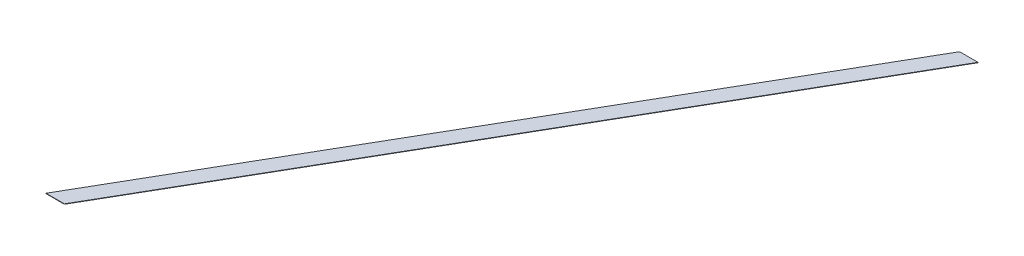
SolidWorks part; units mm, degrees
ref_plane "Front Plane" through (0, 0, 0) normal (0, 0, 1) x (1, 0, 0)
ref_plane "Top Plane" through (0, 0, 0) normal (0, 1, 0) x (1, 0, 0)
ref_plane "Right Plane" through (0, 0, 0) normal (1, 0, 0) x (0, 0, -1)
sketch "Sketch1" plane through (0, 0, 0) normal (0, 1, 0) x (1, 0, 0)
  line L0 (0, 0) -> (0, 101.6615)
  line L1 (0, 101.6615) -> (1523.0785, 2741.8387)
  line L2 (1523.0785, 2741.8387) -> (1581.7255, 2741.8387)
  line L3 (1581.7255, 2741.8387) -> (0, 0)
  line L4 (456.7373, 893.3918) -> (515.3843, 893.3918)
  dimension "D1" = 50.8
  dimension "D2" = 209.98
  dimension "D3" = 3048
  dimension "D4" = 1848.4469
extrude "Boss-Extrude1" add sketch "Sketch1" along normal blind 1.27 contours L1 L4 L3 L2 region at (1019.2314, 0, -1817.6153)
